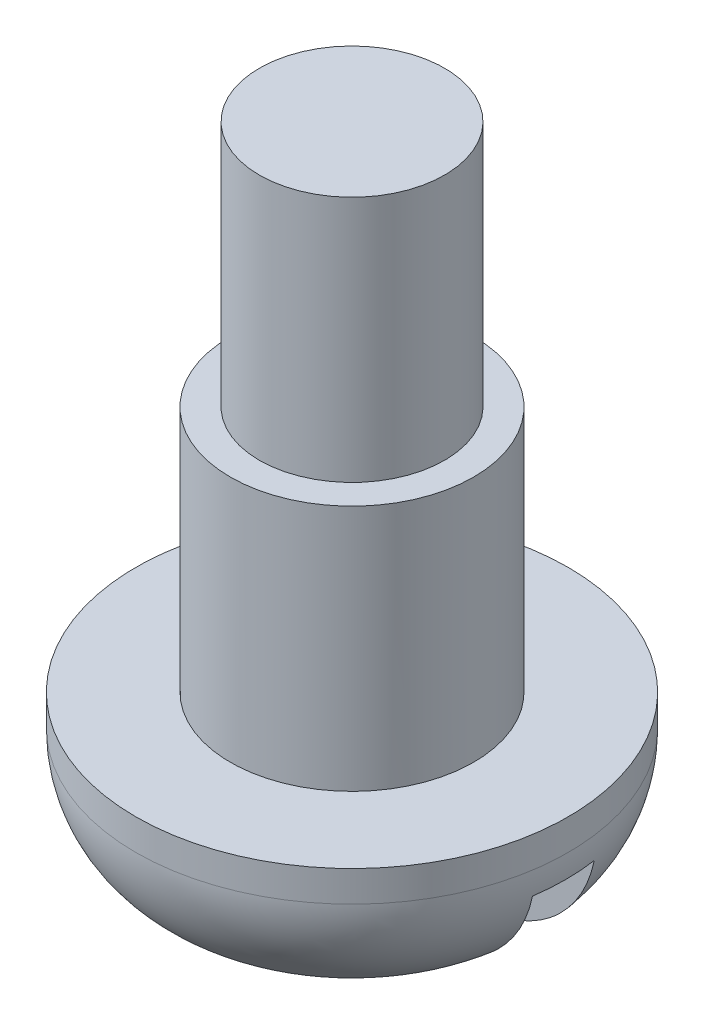
SolidWorks part; units mm, degrees
ref_plane "Piano frontale" through (0, 0, 0) normal (0, 0, 1) x (1, 0, 0)
ref_plane "Piano superiore" through (0, 0, 0) normal (0, 1, 0) x (1, 0, 0)
ref_plane "Piano destro" through (0, 0, 0) normal (1, 0, 0) x (0, 0, -1)
sketch "Schizzo1" plane through (0, 0, 0) normal (0, 1, 0) x (1, 0, 0)
  circle A0 centre (0, 0) radius 1.97
  dimension "D1" = 3.94
extrude "Estrusione-Estrusione1" add sketch "Schizzo1" along normal blind 4
sketch "Schizzo2" plane through (0, 4, 0) normal (0, 1, 0) x (1, 0, 0)
  circle A0 centre (0, 0) radius 1.5
  dimension "D1" = 3
extrude "Estrusione-Estrusione2" add sketch "Schizzo2" along normal blind 4
cosmetic thread "Filettatura cosmetica1" parameters "D2"=2.439
sketch "Schizzo3" plane through (0, 0, 0) normal (0, -1, 0) x (-1, 0, 0)
  circle A0 centre (0, 0) radius 3.5
  dimension "D1" = 7
extrude "Estrusione-Estrusione3" add sketch "Schizzo3" along normal blind 2.5
fillet "Raccordo1" radius 2 1 edges at (0, -2.5, -3.5)
sketch "Schizzo4" plane through (0, -2.5, 0) normal (0, -1, 0) x (1, 0, 0)
  line L1 (-0.5, -1.775) -> (0.5, -1.775)
  line L2 (-0.5, -1.775) -> (-0.5, 1.775)
  line L3 (-0.5, 1.775) -> (0.5, 1.775)
  line L4 (0.5, -1.775) -> (0.5, 1.775)
  line L5 (-0.5, -1.775) -> (0.5, 1.775) construction
  line L6 (-0.5, 1.775) -> (0.5, -1.775) construction
  line L7 (-1.775, -0.5) -> (1.775, -0.5)
  line L8 (-1.775, -0.5) -> (-1.775, 0.5)
  line L9 (-1.775, 0.5) -> (1.775, 0.5)
  line L10 (1.775, -0.5) -> (1.775, 0.5)
  line L11 (-1.775, -0.5) -> (1.775, 0.5) construction
  line L12 (-1.775, 0.5) -> (1.775, -0.5) construction
  point P0 (0, 0)
  point P6 (0, 0)
  circle M1 centre (0, 0) radius 1.5
  dimension "D1" = 3.55
  dimension "D2" = 1
  dimension "D3" = 1
  dimension "D4" = 3.55
extrude "Taglio-Estrusione1" cut sketch "Schizzo4" against normal blind 3 contours L2 L9 L4 M1 | L9 L2 L7 L4 | L4 L3 L2 M1 | L9 L7 L2 M1 | L9 L8 L7 M1 | L7 L2 L4 M1 | L1 L4 L2 M1 | L9 L4 L7 M1 | L7 L10 L9 M1 region at (0, -2.5, -1.6223) region at (0, -2.5, -0.9862) region at (-0.9862, -2.5, 0) region at (0, -2.5, 0) region at (-1.6223, -2.5, 0) region at (0.9862, -2.5, 0) region at (1.6223, -2.5, 0) region at (0, -2.5, 0.9862) region at (0, -2.5, 1.6223)
sketch "Schizzo5" plane through (0, -2.5, 0) normal (0, -1, 0) x (-1, 0, 0)
  line L0 (-0.5, -0.5) -> (-1.775, -0.5) construction
  line L1 (3.5, 0.5) -> (-3.5, 0.5)
  line L2 (3.5, 0.5) -> (3.5, -0.5)
  line L3 (3.5, -0.5) -> (-3.5, -0.5)
  line L4 (-3.5, 0.5) -> (-3.5, -0.5)
  line L5 (3.5, 0.5) -> (-3.5, -0.5) construction
  line L6 (3.5, -0.5) -> (-3.5, 0.5) construction
  circle A0 centre (0, 0) radius 3.5 construction
  point P0 (0, 0)
extrude "Taglio-Estrusione2" cut sketch "Schizzo5" against normal blind 1.6
fillet "Raccordo2" radius 2 2 edges at (1.775, 0.5, 0) (-1.775, 0.5, 0) tangent propagation no
